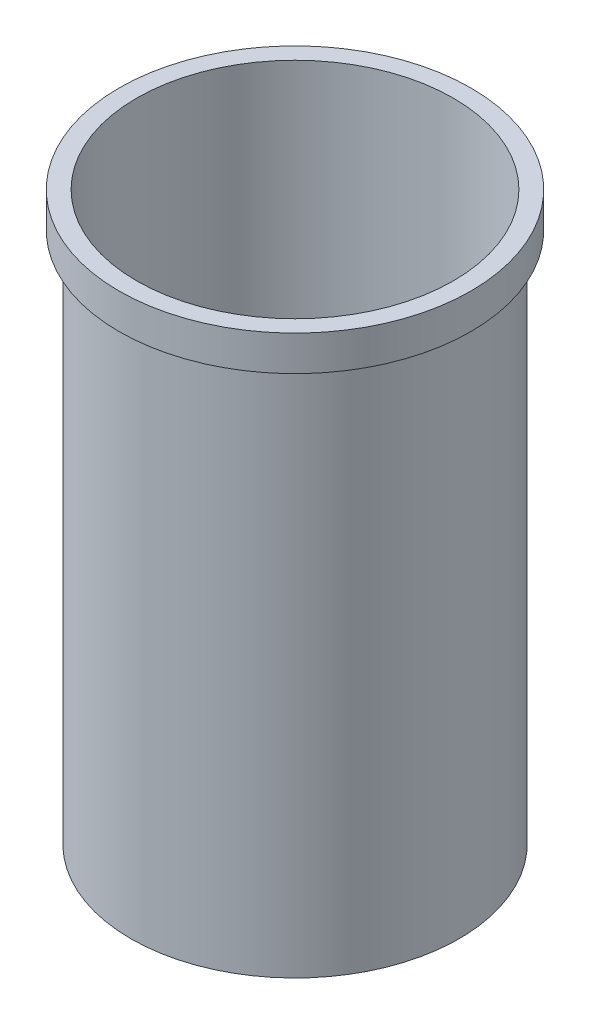
SolidWorks part; units mm, degrees
material "Gray Cast Iron (SN)"
ref_plane "Front Plane" through (0, 0, 0) normal (0, 0, 1) x (1, 0, 0)
ref_plane "Top Plane" through (0, 0, 0) normal (0, 1, 0) x (1, 0, 0)
ref_plane "Right Plane" through (0, 0, 0) normal (1, 0, 0) x (0, 0, -1)
sketch "Sketch1" plane through (0, 0, 0) normal (0, 1, 0) x (1, 0, 0)
  circle A0 centre (0, 0) radius 56.1
  circle A1 centre (0, 0) radius 54.1
  dimension "D1" = 54.1
  dimension "D2" = 2
extrude "Boss-Extrude1" add sketch "Sketch1" along normal blind 193.66
sketch "Sketch3" plane through (0, 193.66, 0) normal (0, 1, 0) x (1, 0, 0)
  circle A0 centre (0, 0) radius 56.1 construction
  circle A1 centre (0, 0) radius 56.1
  circle A2 centre (0, 0) radius 60.1
  dimension "D1" = 4
extrude "Boss-Extrude2" add sketch "Sketch3" against normal blind 12
equation "\"PS_Radius\"= 108 / 2"
equation "\"PS_Clearance\"= 0.1"
equation "\"Liner_Radius\"= \"PS_Clearance\" + \"PS_Radius\""
equation "\"D1@Sketch1\"=\"Liner_Radius\""
equation "\"Liner_Thickness\"= 2"
equation "\"D2@Sketch1\"=\"Liner_Thickness\""
equation "\"Cylinder_Length\" = 181.66 + 12"
equation "\"D1@Boss-Extrude1\"=\"Cylinder_Length\""
equation "\"Lip_Height\"= 12"
equation "\"D1@Boss-Extrude2\"=\"Lip_Height\""
